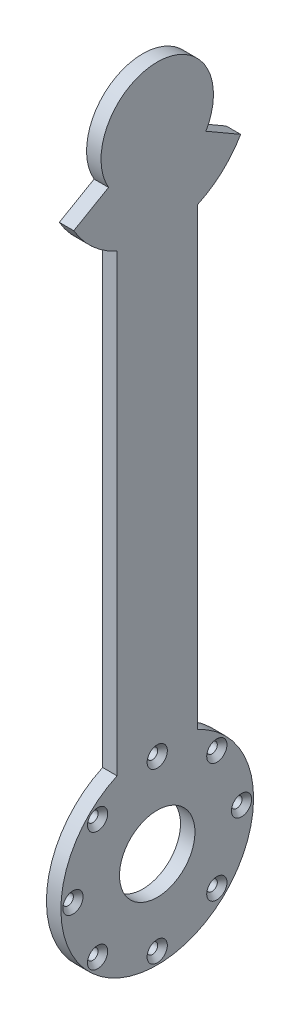
SolidWorks part; units mm, degrees
material "6061 Alloy"
ref_plane "Front Plane" through (0, 0, 0) normal (0, 0, 1) x (1, 0, 0)
ref_plane "Top Plane" through (0, 0, 0) normal (0, 1, 0) x (1, 0, 0)
ref_plane "Right Plane" through (0, 0, 0) normal (1, 0, 0) x (0, 0, -1)
sketch "Sketch1" plane through (0, 0, 0) normal (1, 0, 0) x (0, 0, -1)
  line L0 (0, -196) -> (0, 196) construction
  line L2 (-30.3109, 178.5) -> (-51.9615, 166)
  line L3 (30.3109, 178.5) -> (51.9615, 166)
  line L4 (-25, 141.4564) -> (-25, -141.4564)
  line L5 (25, 141.4564) -> (25, -141.4564)
  arc A1 (-51.9615, 166) -> (-25, 141.4564) centre (0, 196) ccw
  arc A2 (30.3109, 178.5) -> (-30.3109, 178.5) centre (0, 196) ccw
  arc A3 (-25, -141.4564) -> (25, -141.4564) centre (0, -196) ccw
  circle A4 centre (0, -196) radius 23.5
  arc A5 (25, 141.4564) -> (51.9615, 166) centre (0, 196) ccw
  point P4 (0, 0)
  point P9 (0, 196)
  dimension "D2" = 120
  dimension "D3" = 70
  dimension "D5" = 120
  dimension "D6" = 47
  dimension "D1" = 392
extrude "Boss-Extrude1" add sketch "Sketch1" along normal blind 9
sketch "Sketch2" plane through (9, 0, 0) normal (1, 0, 0) x (0, 0, -1)
  circle A0 centre (0, -196) radius 52.5
  arc A1 (-25, -141.4564) -> (25, -141.4564) centre (0, -196) ccw construction
  point P6 (0, -143.5)
  point P7 (37.1231, -158.8769)
  point P10 (52.5, -196)
  point P11 (37.1231, -233.1231)
  point P12 (0, -248.5)
  point P13 (-37.1231, -233.1231)
  point P14 (-52.5, -196)
  point P15 (-37.1231, -158.8769)
  dimension "D1" = 7.5
  dimension "D2" = 8
hole_wizard "CSK for M6 Countersunk Flat Head Screw1" positions "Sketch2" profile "Sketch3" countersink size "M6" standard "ISO" end condition through all
sketch "Sketch3" plane through (9, -158.8769, 37.1231) normal (0, 1, 0) x (0, 0, -1)
  line L0 (0, 0) -> (0, 9)
  line L1 (0, 9) -> (3.3, 9)
  line L2 (3.3, 9) -> (3.3, 3)
  line L3 (3.3, 3) -> (6.3, 0)
  line L5 (6.3, 0) -> (0, 0)
  line L6 (-3.3, 3) -> (-6.3, 0) construction
  line L11 (0, -6.35) -> (0, 107.95) construction
  dimension "Thru Hole Dia." = 6.6
  dimension "Thru Hole Depth" = 9
  dimension "Near C'Sink Dia." = 12.6
  dimension "Near C'Sink Angle" = 90
